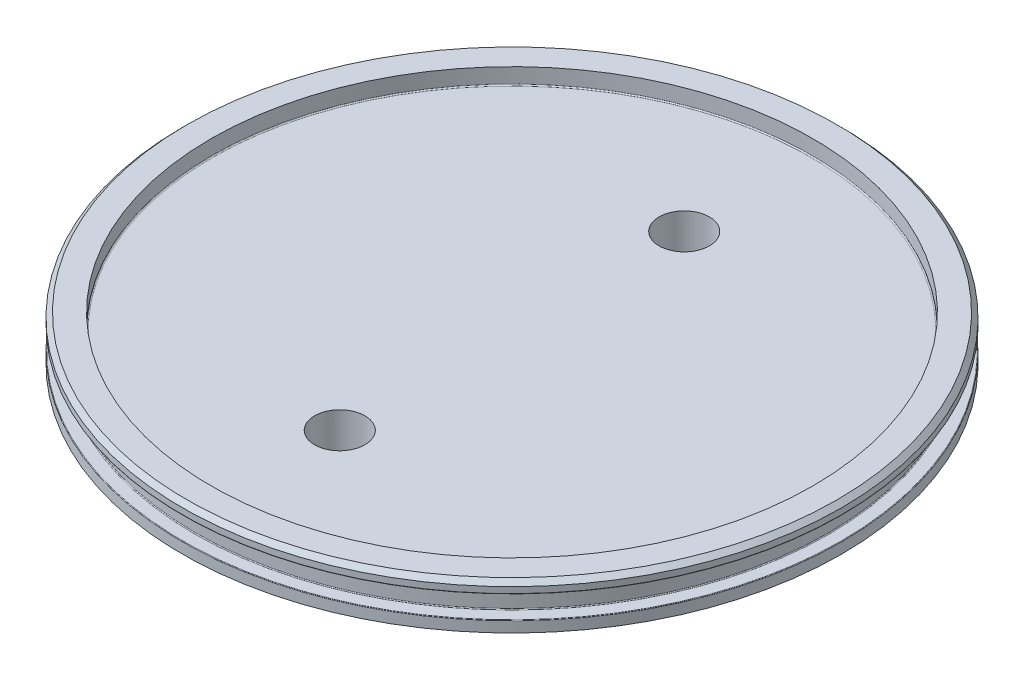
SolidWorks part; units mm, degrees
material "6061-T6 (SS)"
ref_plane "Front Plane" through (0, 0, 0) normal (0, 0, 1) x (1, 0, 0)
ref_plane "Top Plane" through (0, 0, 0) normal (0, 1, 0) x (1, 0, 0)
ref_plane "Right Plane" through (0, 0, 0) normal (1, 0, 0) x (0, 0, -1)
sketch "Sketch1" plane through (0, 0, 0) normal (0, 0, 1) x (1, 0, 0)
  line L0 (0, 48.1922) -> (0, -25.6743) construction
  line L1 (0, 0) -> (72.898, 0)
  line L2 (72.898, 0) -> (72.898, 2.4638)
  line L3 (72.898, 2.4638) -> (69.977, 2.4638)
  line L4 (69.977, 2.4638) -> (69.977, 7.4422)
  line L5 (69.977, 7.4422) -> (72.898, 7.4422)
  line L6 (72.898, 7.4422) -> (72.898, 9.906)
  line L7 (72.898, 9.906) -> (66.548, 9.906)
  line L8 (66.548, 9.906) -> (66.548, 6.35)
  line L9 (66.548, 6.35) -> (0, 6.35)
  line L10 (0, 6.35) -> (0, 0)
  dimension "D1" = 145.796
  dimension "D2" = 4.9784
  dimension "D3" = 2.921
  dimension "D4" = 9.906
  dimension "D5" = 6.35
  dimension "D6" = 6.35
revolve "Revolve1" add sketch "Sketch1" angle 360 about L0
sketch "Sketch6" plane through (0, 0, 0) normal (0, -1, 0) x (1, 0, 0)
  circle A0 centre (0, 0) radius 66.04
  dimension "D1" = 132.08
extrude "Boss-Extrude1" add sketch "Sketch6" along normal blind 2.54
fillet "CNC ID Fillet" radius 0.1778 3 edges at (-69.977, 7.4422, 0) (-69.977, 2.4638, 0) (66.04, 0, 0)
fillet "CNC OD Fillet" radius 0.127 3 edges at (-72.898, 7.4422, 0) (-72.898, 2.4638, 0) (66.04, -2.54, 0)
chamfer "CNC Chamfers" distance 1.016 angle 45 1 edges at (-72.898, 9.906, 0)
fillet "CNC Bore Fillet" radius 0.254 1 edges at (-66.548, 6.35, 0)
hole_wizard "Pipe Tap Drill for 1/4 Tap - Relief Valve" positions "Sketch13" profile "Sketch14" hole size "1/4" standard "ANSI Inch" end condition through all
sketch "Sketch13" plane through (0, -2.54, 0) normal (0, -1, 0) x (-1, 0, 0)
  point P4 (0, 38.1)
  dimension "D1" = 38.1
sketch "Sketch14" plane through (0, -2.54, -38.1) normal (1, 0, 0) x (0, 0, -1)
  line L0 (0, 0) -> (0, 12.446)
  line L1 (0, 12.446) -> (5.5626, 12.446)
  line L2 (5.5626, 12.446) -> (5.5626, 0)
  line L5 (5.5626, 0) -> (0, 0)
  line L11 (0, -6.35) -> (0, 107.95) construction
  dimension "Thru Hole Dia." = 11.1252
  dimension "Thru Hole Depth" = 12.446
hole_wizard "Pipe Tap Drill for 1/4 Tap - Vent Valve" positions "Sketch15" profile "Sketch16" hole size "1/4" standard "ANSI Inch" end condition through all
sketch "Sketch15" plane through (0, -2.54, 0) normal (0, -1, 0) x (-1, 0, 0)
  point P4 (0, -38.1)
  dimension "D1" = 38.1
sketch "Sketch16" plane through (0, -2.54, 38.1) normal (1, 0, 0) x (0, 0, -1)
  line L0 (0, 0) -> (0, 12.446)
  line L1 (0, 12.446) -> (5.5626, 12.446)
  line L2 (5.5626, 12.446) -> (5.5626, 0)
  line L5 (5.5626, 0) -> (0, 0)
  line L11 (0, -6.35) -> (0, 107.95) construction
  dimension "Thru Hole Dia." = 11.1252
  dimension "Thru Hole Depth" = 12.446
